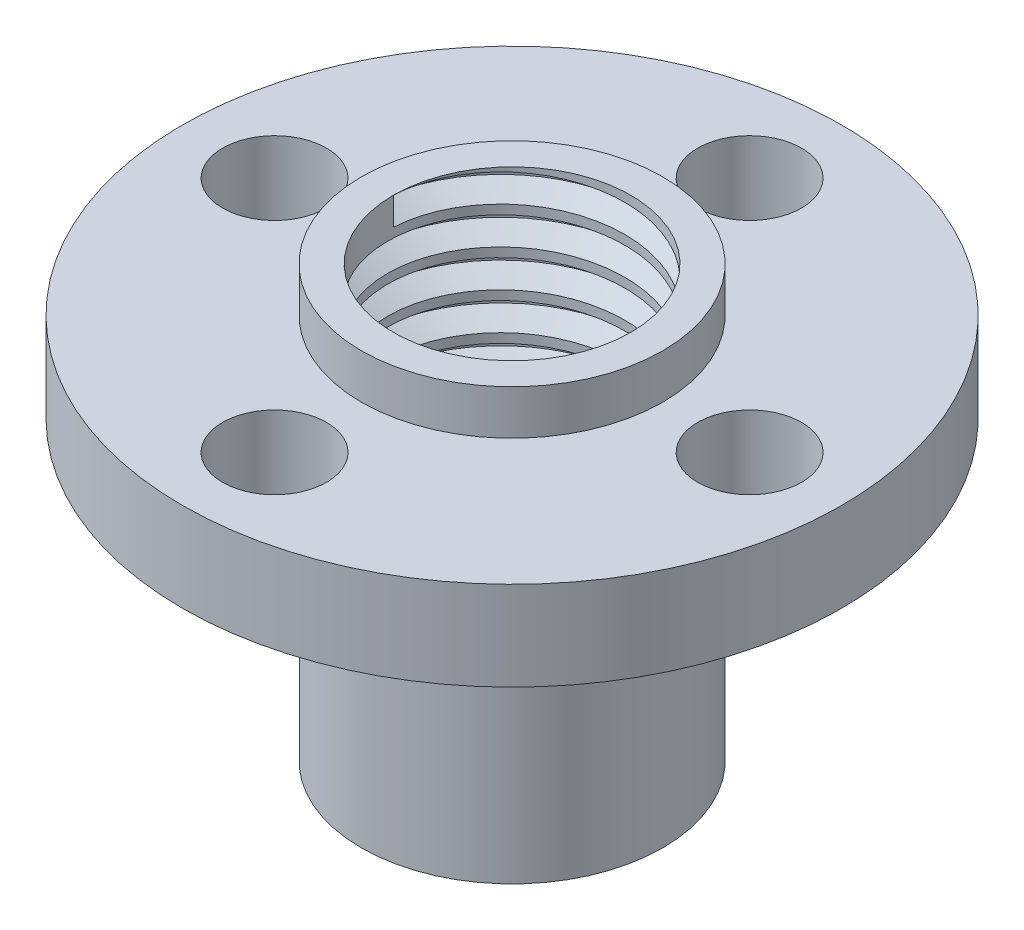
SolidWorks part; units mm, degrees
ref_plane "Front Plane" through (0, 0, 0) normal (0, 0, 1) x (1, 0, 0)
ref_plane "Top Plane" through (0, 0, 0) normal (0, 1, 0) x (1, 0, 0)
ref_plane "Right Plane" through (0, 0, 0) normal (1, 0, 0) x (0, 0, -1)
sketch "Sketch1" plane through (0, 0, 0) normal (0, 1, 0) x (1, 0, 0)
  circle A0 centre (0, 0) radius 4
  circle A1 centre (0, 0) radius 5.075
  dimension "D1" = 8
  dimension "D2" = 10.15
extrude "Boss-Extrude1" add sketch "Sketch1" along normal blind 4.5 and the other way blind 10
sketch "Sketch2" plane through (0, 0, 0) normal (0, 1, 0) x (1, 0, 0)
  line L0 (0, 0) -> (-11.1, 0) construction
  circle A0 centre (0, 0) radius 5.075
  circle A1 centre (0, 0) radius 11.1
  circle A6 centre (-8, 0) radius 1.75
  circle A7 centre (0, 8) radius 1.75
  circle A8 centre (8, 0) radius 1.75
  circle A9 centre (0, -8) radius 1.75
  point P16 (0, 0)
  dimension "D1" = 10.15
  dimension "D2" = 22.2
  dimension "D3" = 3.5
  dimension "D4" = 8
  dimension "D7" = 8
  dimension "D6" = 8
  dimension "D5" = 4
extrude "Boss-Extrude2" add sketch "Sketch2" along normal blind 3
thread "Thread1" pitch 1.25 method cut profile "Thread Profile1" start angle 0, offset 0, length 0, pitch 1.25, diameter 8
ref_plane "Plane1" through (-4, 4.5, 0) normal (0, 0, 1) x (-1, 0, 0)
sketch "Thread Profile1" plane through (-4, 4.5, 0) normal (0, 0, 1) x (-1, 0, 0)
  line L0 (0, 0) -> (0, 1.25) construction
  line L1 (0, 0) -> (0.6766, 0.3906)
  line L2 (0.6766, 0.3906) -> (0.6766, 0.5469)
  line L3 (0.6766, 0.5469) -> (0, 0.9375)
  line L4 (0.6766, 0.4687) -> (0, 0.4687) construction
  line L11 (0, 0) -> (0, 0.9375)
  point P2 (0, 0)
  dimension "Pitch" = 1.25
  dimension "Profile_Angle" = 60
  dimension "Profile_Land" = 0.1562
  dimension "Profile_Height" = 0.6766
